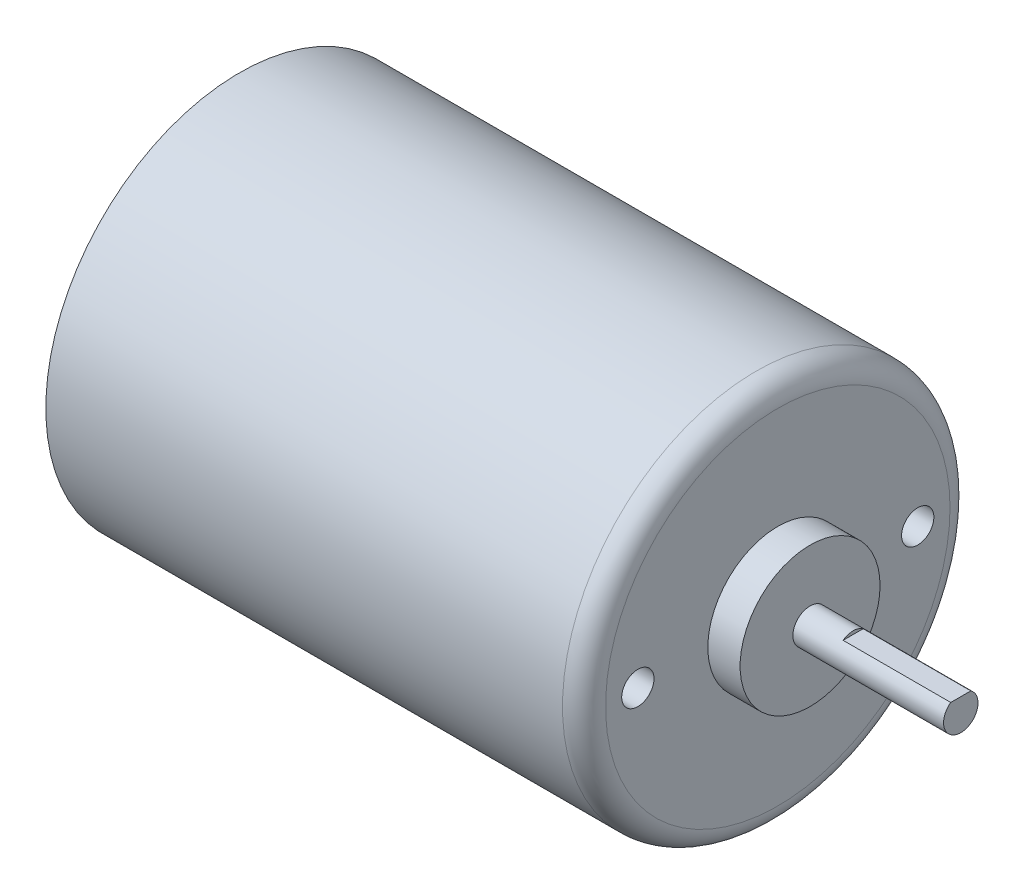
SolidWorks part; units mm, degrees
material "6061 Alloy"
ref_plane "Front Plane" through (0, 0, 0) normal (0, 0, 1) x (1, 0, 0)
ref_plane "Top Plane" through (0, 0, 0) normal (0, 1, 0) x (1, 0, 0)
ref_plane "Right Plane" through (0, 0, 0) normal (1, 0, 0) x (0, 0, -1)
sketch "Sketch1" plane through (0, 0, 0) normal (1, 0, 0) x (0, 0, -1)
  circle A0 centre (0, 0) radius 18
  dimension "D1" = 36
extrude "Boss-Extrude1" add sketch "Sketch1" along normal mid plane 50
sketch "Sketch2" plane through (-25, 0, 0) normal (-1, 0, 0) x (0, 0, 1)
  circle A0 centre (0, 0) radius 17.3
  circle A1 centre (0, 0) radius 18 construction
  dimension "D1" = 0.7
extrude "Cut-Extrude1" cut sketch "Sketch2" against normal blind 0.5
sketch "Sketch3" plane through (-24.5, 0, 0) normal (-1, 0, 0) x (0, 0, 1)
  circle A0 centre (0, 0) radius 12
  dimension "D1" = 24
extrude "Boss-Extrude2" add sketch "Sketch3" along normal mid plane 1
sketch "Sketch4" plane through (-25, 0, 0) normal (-1, 0, 0) x (0, 0, 1)
  circle A0 centre (0, 0) radius 5.125
  dimension "D1" = 10.25
extrude "Boss-Extrude3" add sketch "Sketch4" along normal mid plane 4
fillet "Fillet1" radius 2 1 edges at (25, 0, -18)
sketch "Sketch5" plane through (-24.5, 0, 0) normal (-1, 0, 0) x (0, 0, 1)
  line L0 (0, 0) -> (0, 50000) construction
  line L1 (0, 0) -> (50000, 0) construction
  line L2 (13.52, -2) -> (13, 2) construction
  line L3 (-13.52, 2) -> (-13, 2)
  line L4 (-13.52, 2) -> (-13.52, -2)
  line L5 (-13.52, -2) -> (-13, -2)
  line L6 (-13, 2) -> (-13, -2)
  line L7 (-13.52, 2) -> (-13, -2) construction
  line L8 (-13.52, -2) -> (-13, 2) construction
  line L9 (13.52, 2) -> (13, -2) construction
  line L10 (13, 2) -> (13, -2)
  line L11 (13.52, -2) -> (13, -2)
  line L12 (13.52, 2) -> (13.52, -2)
  line L13 (13.52, 2) -> (13, 2)
  circle A1 centre (0, 0) radius 12 construction
  point P6 (-13.26, 0)
  point P17 (13.26, 0)
  dimension "D2" = 13
  dimension "D1" = 0.52
  dimension "D3" = 4
extrude "Boss-Extrude4" add sketch "Sketch5" along normal mid plane 6
chamfer "Chamfer1" distance 1 angle 45 4 edges at (-27.5, 2, 13.26) (-27.5, -2, 13.26) (-27.5, -2, -13.26) (-27.5, 2, -13.26)
sketch "Sketch6" plane through (25, 0, 0) normal (1, 0, 0) x (0, 0, -1)
  line L0 (0, 0) -> (50000, 0) construction
  line L1 (0, 0) -> (0, 50000) construction
  line L2 (-18, 0) -> (-18, 50000) construction
  circle A0 centre (-13, 0) radius 1.5
  circle A1 centre (0, 0) radius 18 construction
  circle A2 centre (13, 0) radius 1.5
  dimension "D1" = 3
  dimension "D2" = 5
extrude "Cut-Extrude2" cut sketch "Sketch6" against normal blind 6
sketch "Sketch7" plane through (25, 0, 0) normal (1, 0, 0) x (0, 0, -1)
  circle A0 centre (0, 0) radius 6.5
  dimension "D1" = 13
extrude "Boss-Extrude5" add sketch "Sketch7" along normal mid plane 6
sketch "Sketch8" plane through (28, 0, 0) normal (1, 0, 0) x (0, 0, -1)
  circle A0 centre (0, 0) radius 1.6
  dimension "D1" = 3.2
extrude "Boss-Extrude6" add sketch "Sketch8" along normal blind 14
sketch "Sketch9" plane through (42, 0, 0) normal (1, 0, 0) x (0, 0, -1)
  line L0 (-0.9327, 1.3) -> (0.9327, 1.3)
  line L1 (0, 1.6) -> (-50000, 1.6) construction
  circle A0 centre (0, 0) radius 1.6 construction
  arc A1 (0.9327, 1.3) -> (-0.9327, 1.3) centre (0, 0) ccw
  dimension "D1" = 0.3
extrude "Cut-Extrude3" cut sketch "Sketch9" against normal blind 10
